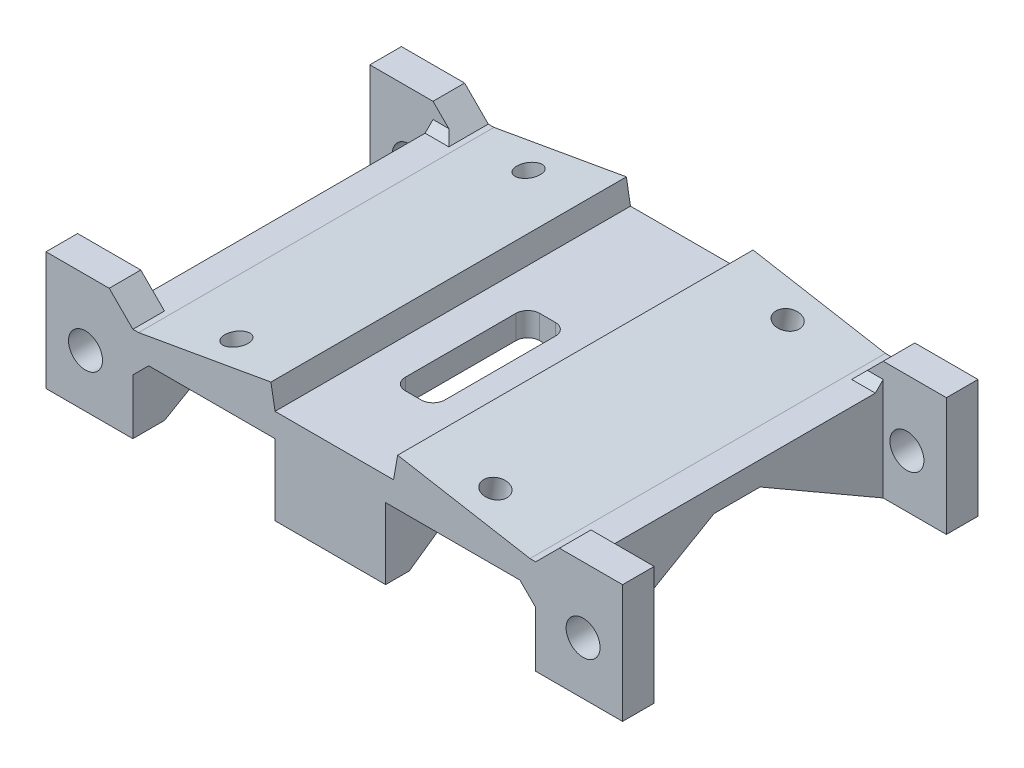
SolidWorks part; units mm, degrees
ref_plane "前视基准面" through (0, 0, 0) normal (0, 0, 1) x (1, 0, 0)
ref_plane "上视基准面" through (0, 0, 0) normal (0, 1, 0) x (1, 0, 0)
ref_plane "右视基准面" through (0, 0, 0) normal (1, 0, 0) x (0, 0, -1)
sketch "草图1" plane through (0, 0, 0) normal (0, 1, 0) x (1, 0, 0)
  line L1 (0, 0) -> (57, 0)
  line L2 (0, 0) -> (0, 45)
  line L3 (0, 45) -> (57, 45)
  line L4 (57, 0) -> (57, 45)
  dimension "D1" = 45
  dimension "D2" = 57
extrude "凸台-拉伸1" add sketch "草图1" along normal blind 3
sketch "草图2" plane through (0, 0, 0) normal (-1, 0, 0) x (0, 0, 1)
  line L0 (0, 6) -> (-4, 6)
  line L1 (-4, 6) -> (-4, -9)
  line L2 (-4, -9) -> (0, -9)
  line L3 (0, -9) -> (0, 6)
  line L4 (-45, 3) -> (0, 3) construction
  line L5 (-45, 0) -> (0, 0) construction
  line L8 (0, 3) -> (0, 0) construction
  dimension "D1" = 3
  dimension "D2" = 9
  dimension "D3" = 4
extrude "凸台-拉伸2" add sketch "草图2" along normal blind 8
sketch "草图3" plane through (57, 0, 0) normal (1, 0, 0) x (0, 0, -1)
  line L0 (0, 6) -> (0, -9)
  line L1 (0, -9) -> (4, -9)
  line L2 (4, -9) -> (4, 6)
  line L3 (4, 6) -> (0, 6)
extrude "凸台-拉伸3" add sketch "草图3" along normal blind 8
sketch "草图4" plane through (57, 0, 0) normal (-1, 0, 0) x (0, 0, 1)
  line L0 (-4, -9) -> (-19.5885, 0)
  line L1 (-4, 0) -> (-45, 0) construction
  line L2 (-19.5885, 0) -> (0, 0)
  line L3 (0, 0) -> (0, -9)
  line L4 (0, -9) -> (-4, -9)
  dimension "D1" = 30
extrude "凸台-拉伸4" add sketch "草图4" along normal blind 3
sketch "草图5" plane through (0, 0, 0) normal (1, 0, 0) x (0, 0, -1)
  line L0 (0, 0.3045) -> (0, -9)
  line L1 (0, -9) -> (4, -9)
  line L2 (4, -9) -> (19.5885, 0)
  line L3 (45, 0) -> (4, 0) construction
  line L4 (19.5885, 0) -> (0, 0)
  line M3 (4, -9) -> (4, 0)
  line M4 (4, 0) -> (0, 0)
  line M5 (0, 0) -> (0, -9)
  line M6 (0, -9) -> (4, -9)
  dimension "D1" = 30
extrude "凸台-拉伸5" add sketch "草图5" along normal blind 3 contours L2 L4 M3 | M6 M3 M4 M5 region at (0, -4.5, -2) region at (0, -3, -9.1962)
chamfer "倒角1" distance 3 angle 45 2 edges at (0, 3, -2) (57, 3, -2)
sketch "草图6" plane through (0, 0, -4) normal (0, 0, -1) x (-1, 0, 0)
  line L0 (-60, -2.3233) -> (3, -2.3233) construction
  line L3 (-28.5, 0) -> (-28.5, 11.0492) construction
  line L4 (-57, 0) -> (0, 0) construction
  line L5 (-65, -9) -> (-57, -9) construction
  circle A0 centre (3, -2.3233) radius 2.15
  circle A1 centre (-60, -2.3233) radius 2.15
  dimension "D1" = 31.5
  dimension "D2" = 6.6767
  dimension "D3" = 4.3
extrude "切除-拉伸1" cut sketch "草图6" against normal blind 4
sketch "草图7" plane through (0, 3, 0) normal (0, 1, 0) x (1, 0, 0)
  line L0 (28, 49.7957) -> (28, -5.721) construction
  line L1 (8, 41) -> (8, 4)
  line L2 (3, 0) -> (54, 0) construction
  line L3 (0, 45) -> (0, 4) construction
  line L4 (48, 41) -> (48, 4)
  circle A0 centre (8, 41) radius 1.6
  circle A1 centre (8, 4) radius 1.6
  circle A2 centre (48, 4) radius 1.6
  circle A3 centre (48, 41) radius 1.6
  dimension "D1" = 37
  dimension "D2" = 4
  dimension "D3" = 8
extrude "切除-拉伸2" [suppressed] cut sketch "草图7" against normal blind 3 contours A3 | A2 | A0 | A1
sketch "草图8" plane through (0, 0, 0) normal (0, -1, 0) x (1, 0, 0)
  line L0 (24, -45) -> (32, -45)
  line L1 (57, -45) -> (0, -45) construction
  line L2 (32, -45) -> (32, -42)
  line L3 (32, -42) -> (24, -42)
  line L4 (24, -42) -> (24, -45)
  line L5 (28, 5.34) -> (28, -50.6665) construction
  line L6 (0, -45) -> (0, -19.5885) construction
  point P10 (32, -43.5)
  dimension "D1" = 28
  dimension "D2" = 3
  dimension "D3" = 8
  dimension "D4" = 4
extrude "凸台-拉伸6" add sketch "草图8" along normal blind 9
sketch "草图9" plane through (32, 0, 0) normal (1, 0, 0) x (0, 0, -1)
  line L0 (45, 0) -> (29.1467, 0)
  line L1 (29.1467, 0) -> (42, -9)
  line L2 (42, -9) -> (45, -9)
  line L3 (45, -9) -> (45, 0)
  dimension "D1" = 35
extrude "凸台-拉伸7" add sketch "草图9" along normal blind 3
sketch "草图10" plane through (24, 0, 0) normal (-1, 0, 0) x (0, 0, 1)
  line L0 (-45, 0) -> (-45, -9)
  line L1 (-45, -9) -> (-42, -9)
  line L2 (-42, -9) -> (-29.1467, 0)
  line L3 (-29.1467, 0) -> (-45, 0)
extrude "凸台-拉伸8" add sketch "草图10" along normal blind 3
sketch "草图11" plane through (0, 0, -42) normal (0, 0, 1) x (1, 0, 0)
  line L0 (24, -9) -> (24, 0) construction
  line L1 (32, -9) -> (24, -9) construction
  circle A0 centre (28, -4.5) radius 1.6
  dimension "D1" = 4
  dimension "D2" = 4.5
extrude "切除-拉伸3" [suppressed] cut sketch "草图11" against normal blind 3
sketch "草图12" plane through (0, 3, 0) normal (0, 1, 0) x (1, 0, 0)
  line L0 (28, 49.4691) -> (28, -3.816) construction
  line L1 (25.5, 27.5) -> (25.5, 10.5)
  line L2 (25.5, 10.5) -> (30.5, 10.5)
  line L3 (30.5, 10.5) -> (30.5, 27.5)
  line L4 (30.5, 27.5) -> (25.5, 27.5)
  line L5 (0, 45) -> (0, 4) construction
  line L6 (-5.009, 22.5) -> (59.3487, 22.5) construction
  line L7 (3, 0) -> (54, 0) construction
  dimension "D1" = 28
  dimension "D2" = 2.5
  dimension "D3" = 2.5
  dimension "D4" = 22.5
  dimension "D5" = 5
  dimension "D6" = 12
extrude "切除-拉伸4" cut sketch "草图12" against normal blind 3
fillet "圆角1" radius 1.5 4 edges at (30.5, 1.5, -10.5) (25.5, 1.5, -10.5) (25.5, 1.5, -27.5) (30.5, 1.5, -27.5)
ref_plane "基准面1" through (28.5, 0, 0) normal (1, 0, 0) x (0, 0, -1)
sketch "草图13" plane through (0, 3, 0) normal (0, 1, 0) x (1, 0, 0)
  line L0 (36, 45) -> (36, 0) construction
  line L1 (57, 45) -> (0, 45) construction
  line L2 (3, 0) -> (54, 0) construction
  line L3 (57, 4) -> (57, 45) construction
  dimension "D1" = 21
ref_plane "基准面2" through (34.4014, -6.0659, 0) normal (0.9848, -0.1736, 0) x (0, 0, 1)
sketch "草图14" plane through (34.4014, -6.0659, 0) normal (0.9848, -0.1736, 0) x (0, 0, 1)
  line L0 (-45, -9.2058) -> (0, -9.2058) construction
  line L1 (-45, -9.2058) -> (0, -9.2058) construction
  line L3 (-45, -9.2058) -> (0, -9.2058) construction
  line L4 (-45, -9.2058) -> (-45, -12.2058) construction
  line L5 (-45, -12.2058) -> (0, -12.2058) construction
  line L6 (0, -9.2058) -> (0, -12.2058) construction
  dimension "D1" = 3
ref_plane "基准面3" through (2.1195, 12.0203, 0) normal (0.1736, 0.9848, 0) x (0, 0, 1)
sketch "草图15" plane through (2.1195, 12.0203, 0) normal (0.1736, 0.9848, 0) x (0, 0, 1)
  line L1 (-45, 34.9321) -> (0, 34.9321)
  line L2 (-45, 34.9321) -> (-45, 52.6587)
  line L3 (-45, 52.6587) -> (0, 52.6587)
  line L4 (0, 34.9321) -> (0, 52.6587)
extrude "凸台-拉伸9" add sketch "草图15" against normal up to body separate body
sketch "草图16" plane through (2.1195, 12.0203, 0) normal (0.1736, 0.9848, 0) x (0.9848, -0.1736, 0)
  line L0 (43.4391, 45) -> (43.4391, 0) construction
  line L1 (51.946, 45) -> (34.9321, 45) construction
  line L2 (34.9321, 0) -> (51.946, 0) construction
  line L3 (51.946, 22.5) -> (43.4391, 22.5) construction
  line L4 (51.946, 45) -> (51.946, 0) construction
  circle A0 centre (43.4391, 41) radius 1.5
  circle A1 centre (43.4391, 4) radius 1.5
  dimension "D1" = 3
  dimension "D2" = 18.5
extrude "切除-拉伸5" cut sketch "草图16" against normal through all
mirror "镜向1" about plane through (28.5, 0, 0) normal (1, 0, 0) of "切除-拉伸5", "凸台-拉伸9"
ref_plane "基准面4" through (0, 0, -22.5) normal (0, 0, 1) x (1, 0, 0)
mirror "镜向2" about plane through (0, 0, -22.5) normal (0, 0, 1) of "倒角1", "凸台-拉伸5", "凸台-拉伸4", "凸台-拉伸3", "凸台-拉伸2", "切除-拉伸1"
mirror "镜向3" about plane through (0, 0, -22.5) normal (0, 0, 1) of "凸台-拉伸7", "凸台-拉伸6", "凸台-拉伸8"
chamfer "倒角2" distance 1 angle 45 2 edges at (1.5, 3, -41) (55.5, 3, -41)
chamfer "倒角3" distance 2 angle 45 4 edges at (54, 0, -9.7942) (54, 0, -35.2058) (3, 0, -35.2058) (3, 0, -9.7942)
